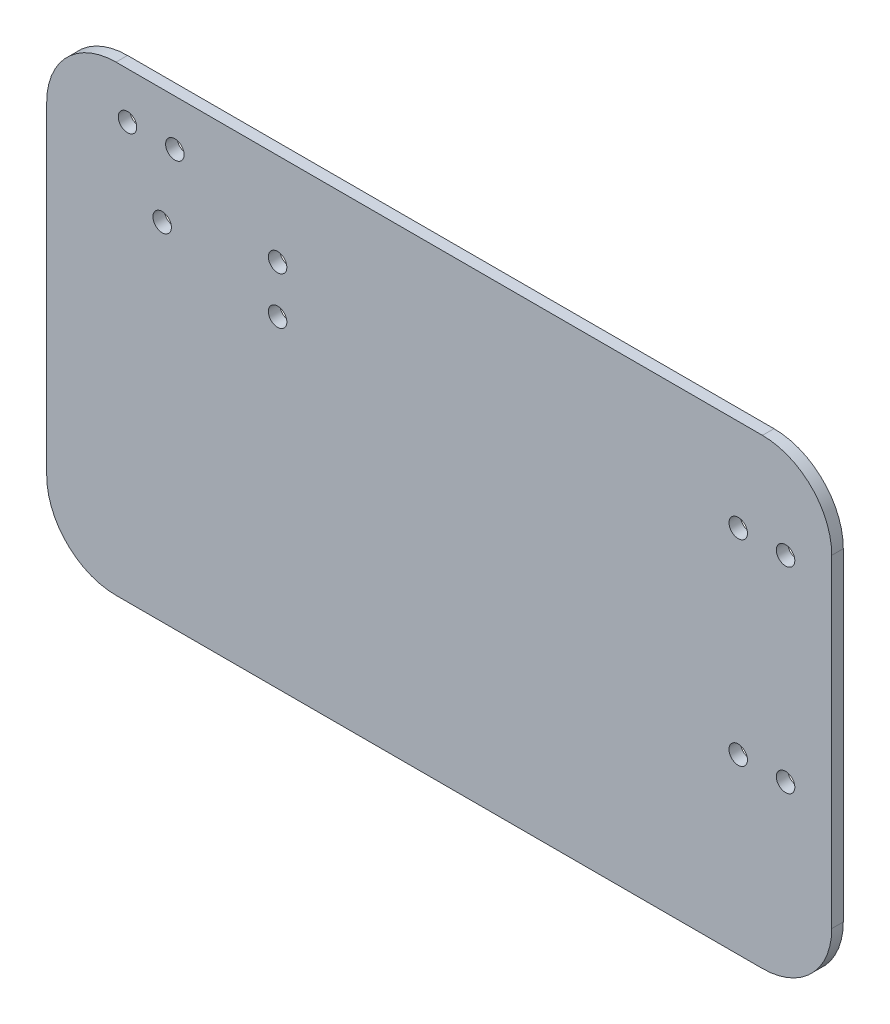
SolidWorks part; units mm, degrees
ref_plane "Alzado" through (0, 0, 0) normal (0, 0, 1) x (1, 0, 0)
ref_plane "Planta" through (0, 0, 0) normal (0, 1, 0) x (1, 0, 0)
ref_plane "Vista lateral" through (0, 0, 0) normal (1, 0, 0) x (0, 0, -1)
sketch "Croquis1" plane through (0, 0, 0) normal (0, 0, 1) x (1, 0, 0)
  line L0 (-125.4724, -88.3321) -> (154.5276, -88.3321)
  line L1 (184.5276, -58.3321) -> (184.5276, 81.6679)
  line L2 (154.5276, 111.6679) -> (-125.4724, 111.6679)
  line L3 (-155.4724, 81.6679) -> (-155.4724, -58.3321)
  arc A0 (-155.4724, -58.3321) -> (-125.4724, -88.3321) centre (-125.4724, -58.3321) ccw
  arc A1 (154.5276, -88.3321) -> (184.5276, -58.3321) centre (154.5276, -58.3321) ccw
  arc A2 (184.5276, 81.6679) -> (154.5276, 111.6679) centre (154.5276, 81.6679) ccw
  arc A3 (-125.4724, 111.6679) -> (-155.4724, 81.6679) centre (-125.4724, 81.6679) ccw
  circle A4 centre (-105.4724, 61.6679) radius 4
  circle A5 centre (-55.4724, 71.6679) radius 4
  circle A6 centre (-55.4724, 51.1679) radius 4
  circle A7 centre (144.0276, -13.3321) radius 4
  circle A8 centre (164.5276, -13.3321) radius 4
  circle A9 centre (144.0276, 71.6679) radius 4
  circle A10 centre (164.5276, 71.6679) radius 4
  circle A11 centre (-99.9724, 91.6679) radius 4
  circle A12 centre (-120.4724, 91.6679) radius 4
  dimension "D1" = 8
  dimension "D2" = 30
  dimension "D3" = 144.0276
  dimension "D4" = 164.5276
  dimension "D5" = 184.5276
  dimension "D6" = 55.4724
  dimension "D7" = 99.9724
  dimension "D8" = 105.4724
  dimension "D9" = 120.4724
  dimension "D10" = 155.4724
  dimension "D11" = 51.1679
  dimension "D12" = 61.6679
  dimension "D13" = 71.6679
  dimension "D14" = 91.6679
  dimension "D15" = 111.6679
  dimension "D16" = 13.3321
  dimension "D17" = 88.3321
extrude "Saliente-Extruir1" add sketch "Croquis1" along normal blind 5
